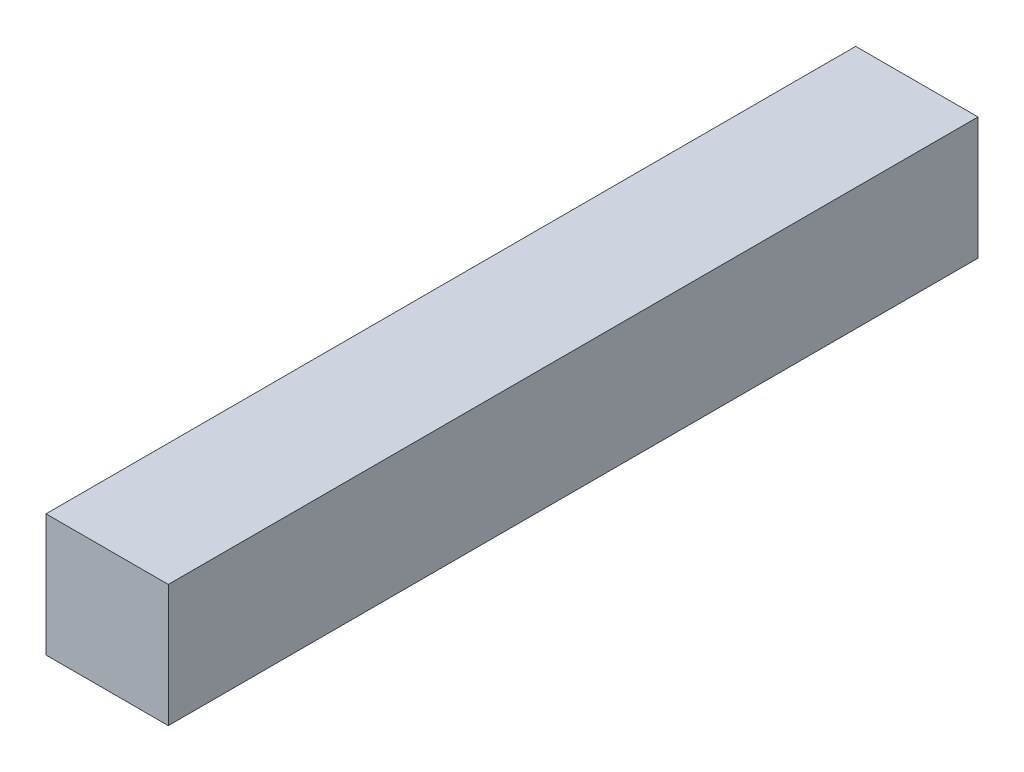
SolidWorks part; units mm, degrees
ref_plane "Plan de face" through (0, 0, 0) normal (0, 0, 1) x (1, 0, 0)
ref_plane "Plan de dessus" through (0, 0, 0) normal (0, 1, 0) x (1, 0, 0)
ref_plane "Plan de droite" through (0, 0, 0) normal (1, 0, 0) x (0, 0, -1)
sketch "Esquisse1" plane through (0, 0, 0) normal (0, 0, 1) x (1, 0, 0)
  line L0 (-5, 5) -> (5, -5) construction
  line L1 (-5, 5) -> (5, 5)
  line L2 (-5, 5) -> (-5, -5)
  line L3 (-5, -5) -> (5, -5)
  line L4 (5, 5) -> (5, -5)
  dimension "D1" = 10
extrude "Boss.-Extru.1" add sketch "Esquisse1" along normal offset from surface (66.2 mm away) 2 offset beyond the face yes
